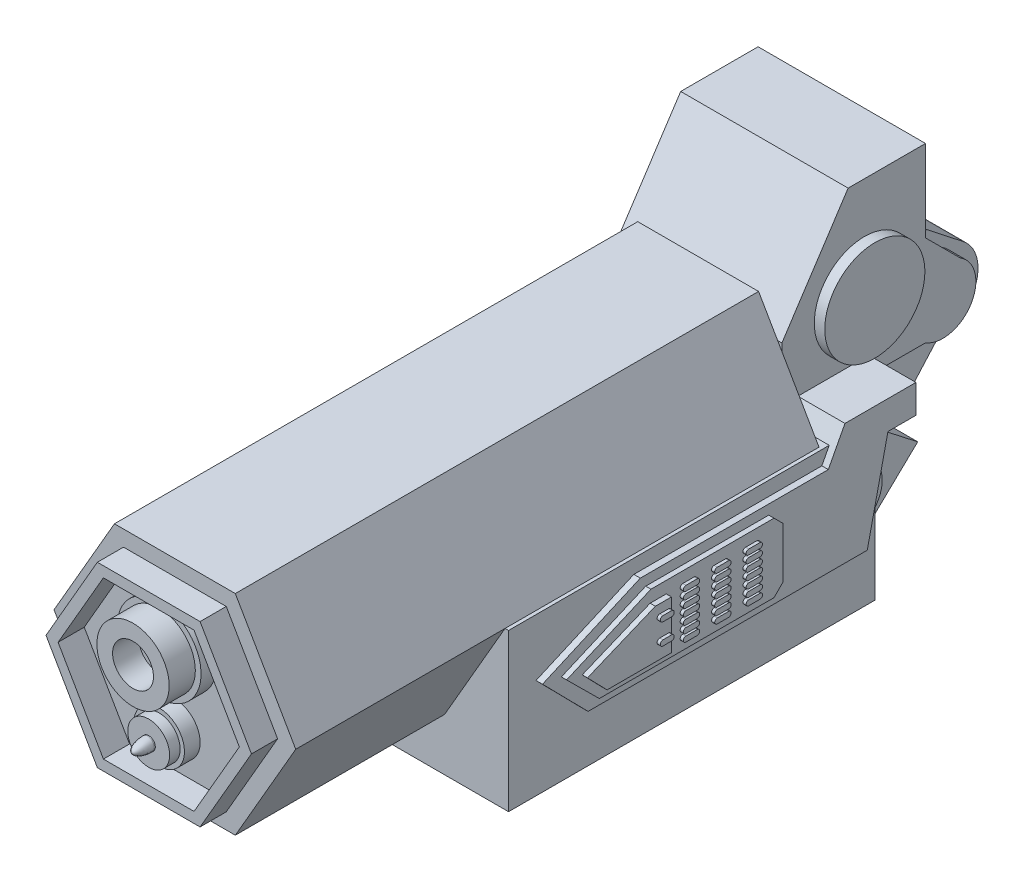
SolidWorks part; units mm, degrees
ref_plane "Front Plane" through (0, 0, 0) normal (0, 0, 1) x (1, 0, 0)
ref_plane "Top Plane" through (0, 0, 0) normal (0, 1, 0) x (1, 0, 0)
ref_plane "Right Plane" through (0, 0, 0) normal (1, 0, 0) x (0, 0, -1)
sketch "Sketch1" plane through (0, 0, 0) normal (0, 0, 1) x (1, 0, 0)
  line L0 (0, 0) -> (-46.0761, 0) construction
  line L1 (14.6647, 25.4) -> (-14.6647, 25.4)
  line L2 (-14.6647, 25.4) -> (-29.3294, 0)
  line L3 (-29.3294, 0) -> (-14.6647, -25.4)
  line L4 (-14.6647, -25.4) -> (14.6647, -25.4)
  line L5 (14.6647, -25.4) -> (29.3294, 0)
  line L6 (29.3294, 0) -> (14.6647, 25.4)
  circle A0 centre (0, 0) radius 25.4 construction
extrude "Boss-Extrude1" add sketch "Sketch1" against normal blind 127
sketch "Sketch2" plane through (0, 0, 0) normal (0, 0, 1) x (1, 0, 0)
  line L0 (14.6647, 25.4) -> (-14.6647, 25.4) construction
  line L1 (10.9985, 19.05) -> (-10.9985, 19.05)
  line L2 (-10.9985, 19.05) -> (-21.997, 0)
  line L3 (-21.997, 0) -> (-10.9985, -19.05)
  line L4 (-10.9985, -19.05) -> (10.9985, -19.05)
  line L5 (10.9985, -19.05) -> (21.997, 0)
  line L6 (21.997, 0) -> (10.9985, 19.05)
  circle A0 centre (0, 0) radius 19.05 construction
  dimension "D1" = 38.1
extrude "Extrude-Thin1" add sketch "Sketch2" along normal blind 6.35 thin thin type one direction wall 2.54
sketch "Sketch3" plane through (0, 0, 0) normal (0, 0, 1) x (1, 0, 0)
  line L0 (0, 0) -> (0, 26.4435) construction
  circle A0 centre (0, 8.1531) radius 10.16
  circle A1 centre (0, -10.2056) radius 6.131
extrude "Boss-Extrude2" add sketch "Sketch3" along normal blind 3.81
sketch "Sketch4" plane through (0, 0, 3.81) normal (0, 0, 1) x (1, 0, 0)
  circle A0 centre (0, 8.1531) radius 8.771
extrude "Extrude-Thin2" add sketch "Sketch4" along normal blind 6.35 thin thin type one direction reverse wall 3.81
sketch "Sketch5" plane through (0, 0, 3.81) normal (0, 0, 1) x (1, 0, 0)
  circle A0 centre (0, -10.2056) radius 5.08
extrude "Boss-Extrude3" add sketch "Sketch5" along normal blind 2.54
sketch "Sketch6" plane through (0, 0, 6.35) normal (0, 0, 1) x (1, 0, 0)
  circle A0 centre (0, -10.2056) radius 1.5996
extrude "Boss-Extrude4" add sketch "Sketch6" along normal blind 0.254
dome "Dome2" faces to dome 1 distance 3.81 reverse direction no elliptical dome yes face at (1.5996, -10.2056, 6.604) parameters "D1"=3.81
sketch "Sketch7" plane through (0, 0, 0) normal (0, 0, 1) x (1, 0, 0)
  line L0 (0, 0) -> (-37.4831, 0) construction
  line L1 (-30.3495, 0) -> (30.1809, 0)
  line L2 (-30.3495, 0) -> (-30.3495, -38.1)
  line L3 (-30.3495, -38.1) -> (30.1809, -38.1)
  line L4 (30.1809, 0) -> (30.1809, -38.1)
  dimension "D1" = 38.1
extrude "Boss-Extrude5" add sketch "Sketch7" against normal blind 88.9 from offset 50.8 offset against normal yes
sketch "Sketch8" plane through (0, 0, 0) normal (1, 0, 0) x (0, 0, -1)
  line L0 (139.7, -19.05) -> (156.755, -19.05)
  line L1 (139.7, 0) -> (139.7, -38.1) construction
  line L2 (156.755, -19.05) -> (169.6659, -4.4991)
  line L3 (139.7, -19.05) -> (139.7, 0)
  line L4 (139.7, 0) -> (166.5054, 19.2853)
  line L5 (166.5054, 19.2853) -> (175.4567, 12.2619)
  arc A0 (169.6659, -4.4991) -> (175.4567, 12.2619) centre (169.6661, 4.8817) ccw
extrude "Boss-Extrude6" add sketch "Sketch8" along normal blind 15.875 and the other way blind 15.875
sketch "Sketch9" plane through (0, 0, 0) normal (1, 0, 0) x (0, 0, -1)
  line L0 (127, 17.3963) -> (143.0783, 41.9028)
  line L1 (127, 25.4) -> (127, 0) construction
  line L2 (143.0783, 41.9028) -> (161.8606, 41.9028)
  line L3 (161.8606, 41.9028) -> (161.8606, 22.0472)
  line L4 (161.8606, 22.0472) -> (170.2679, 13.6399)
  line L5 (127, 17.3963) -> (127, 0)
  line L6 (127, 0) -> (161.8606, 0)
  arc A0 (161.8606, 0) -> (170.2679, 13.6399) centre (166.0643, 6.8199) ccw
extrude "Boss-Extrude7" add sketch "Sketch9" along normal blind 20.32 and the other way blind 20.32
sketch "Sketch10" plane through (0, 0, 0) normal (1, 0, 0) x (0, 0, -1)
  circle A0 centre (147.0136, 17.5982) radius 12.1559
extrude "Boss-Extrude8" add sketch "Sketch10" along normal blind 22.86 and the other way blind 22.86
sketch "Sketch11" plane through (0, 0, 0) normal (1, 0, 0) x (0, 0, -1)
  line L0 (139.7, -19.05) -> (139.7, -38.1)
  line L1 (139.7, -38.1) -> (156.4942, -38.1)
  line L2 (156.4942, -38.1) -> (167.5847, -27.4794)
  line L3 (167.5847, -27.4794) -> (156.755, -19.05)
  line L4 (156.755, -19.05) -> (139.7, -19.05)
extrude "Boss-Extrude9" add sketch "Sketch11" along normal blind 12.7 and the other way blind 12.7
sketch "Sketch12" plane through (0, 0, 0) normal (1, 0, 0) x (0, 0, -1)
  circle A0 centre (148.7813, -28.6662) radius 7.6511
extrude "Boss-Extrude10" add sketch "Sketch12" along normal blind 15.24 and the other way blind 15.24
sketch "Sketch13" plane through (0, -38.1, 0) normal (0, -1, 0) x (1, 0, 0)
  line L0 (0, -50.8) -> (0, -161.0568) construction
  line L1 (14.6647, -50.8) -> (-14.6647, -50.8) construction
  line L2 (-30.3495, -95.25) -> (33.7635, -95.25) construction
  line L3 (-30.3495, -139.7) -> (-30.3495, -50.8) construction
  line L5 (-17.9147, -147.0136) -> (17.9147, -147.0136)
  line L6 (-17.9147, -147.0136) -> (-17.9147, -64.8432)
  line L7 (-17.9147, -64.8432) -> (17.9147, -64.8432)
  line L8 (17.9147, -147.0136) -> (17.9147, -64.8432)
  line L9 (-17.9147, -147.0136) -> (17.9147, -64.8432) construction
  line L10 (-17.9147, -64.8432) -> (17.9147, -147.0136) construction
  point P9 (0, -105.9284)
ref_plane "Plane1" through (0, -57.15, 0) normal (0, -1, 0) x (1, 0, 0)
sketch "Sketch14" plane through (0, -57.15, 0) normal (0, -1, 0) x (1, 0, 0)
  line L1 (-8.56, -137.842) -> (8.56, -137.842)
  line L2 (-8.56, -137.842) -> (-8.56, -74.0148)
  line L3 (-8.56, -74.0148) -> (8.56, -74.0148)
  line L4 (8.56, -137.842) -> (8.56, -74.0148)
  line L5 (-8.56, -137.842) -> (8.56, -74.0148) construction
  line L6 (-8.56, -74.0148) -> (8.56, -137.842) construction
  point P0 (0, -105.9284)
loft "Loft1" add profiles "Sketch13", "Sketch14" connector at (17.9147, -38.1, -64.8432) connector at (8.56, -57.15, -74.0148)
sketch "Sketch15" plane through (0, 18.1746, -37.7498) normal (0, -0.4338, 0.901) x (1, 0, 0)
  line L0 (-10.7029, -62.4571) -> (0, -82.542)
  line L1 (-17.9147, -62.4571) -> (17.9147, -62.4571) construction
  line L2 (-10.7029, -62.4571) -> (10.7029, -62.4571)
  line L3 (17.9147, -62.4571) -> (-17.9147, -62.4571) construction
  line L4 (0, -62.4571) -> (0, -82.542) construction
  line L5 (10.7029, -62.4571) -> (0, -82.542)
extrude "Boss-Extrude11" add sketch "Sketch15" along normal blind 1.27
sketch "Sketch16" plane through (0, 17.6237, -36.6055) normal (0, -0.4338, 0.901) x (1, 0, 0)
  line L0 (10.7029, -62.4571) -> (-10.7029, -62.4571) construction
  line L1 (-10.7029, -62.4571) -> (-5.8753, -62.4571) construction
  line L2 (5.8753, -62.4571) -> (10.7029, -62.4571) construction
  line L3 (-5.8753, -62.4571) -> (5.8753, -62.4571)
  line L7 (-5.8753, -62.4571) -> (0, -79.4472)
  line L8 (0, -79.4472) -> (5.8753, -62.4571)
extrude "Boss-Extrude12" add sketch "Sketch16" along normal blind 2.54
fillet "Fillet1" radius 1.27 2 edges at (0, -56.4722, -72.9837) (0, -54.5102, -69.9248)
sketch "Sketch17" plane through (0, 0, 0) normal (1, 0, 0) x (0, 0, -1)
  line L0 (68.5306, -25.0933) -> (136.2912, -25.0933)
  line L1 (136.2912, -25.0933) -> (141.3068, -2.6485)
  line L2 (148.0979, -2.6485) -> (148.0979, 4.2639)
  line L3 (148.0979, 4.2639) -> (130.8775, 4.2639)
  line L4 (130.8775, 4.2639) -> (126.8356, -3.4158)
  line L5 (126.8356, -3.4158) -> (81.2052, -3.4158)
  line L6 (81.2052, -3.4158) -> (57.4673, -13.8461)
  line L7 (57.4673, -13.8461) -> (68.5306, -25.0933)
  line L8 (148.0979, -2.6485) -> (141.3068, -2.6485)
extrude "Boss-Extrude13" add sketch "Sketch17" along normal blind 31.75 and the other way blind 31.75
sketch "Sketch18" plane through (-31.75, 0, 0) normal (-1, 0, 0) x (0, 0, 1)
  line L0 (-112.3819, -22.4812) -> (-69.988, -22.4812)
  line L1 (-69.988, -22.4812) -> (-62.0481, -14.5993)
  line L2 (-62.0481, -14.5993) -> (-82.5216, -5.7665)
  line L3 (-82.5216, -5.7665) -> (-112.3819, -5.7665)
  line L4 (-114.5712, -7.9558) -> (-114.5712, -20.2918)
  line L5 (-112.3819, -5.7665) -> (-114.5712, -7.9558)
  line L6 (-114.5712, -20.2918) -> (-112.3819, -22.4812)
extrude "Boss-Extrude14" add sketch "Sketch18" along normal blind 1.27
sketch "Sketch19" plane through (-33.02, 0, 0) normal (-1, 0, 0) x (0, 0, 1)
  line L0 (-86.2319, -20.3383) -> (-70.6018, -20.3383)
  line L1 (-70.6018, -20.3383) -> (-65.8448, -15.4356)
  line L2 (-65.8448, -15.4356) -> (-82.3244, -8.6157)
  line L3 (-82.3244, -8.6157) -> (-86.2319, -8.6157)
  line L4 (-86.2319, -8.6157) -> (-86.2319, -20.3383)
extrude "Boss-Extrude15" add sketch "Sketch19" along normal blind 1.27
sketch "Sketch20" plane through (-34.29, 0, 0) normal (-1, 0, 0) x (0, 0, 1)
  line L0 (-85.4907, -11.4026) -> (-83.3959, -11.4026) construction
  line L1 (-85.4907, -10.752) -> (-83.3959, -10.752)
  line L2 (-85.4907, -12.0533) -> (-83.3959, -12.0533)
  line L3 (-85.4907, -16.4826) -> (-83.3959, -16.4826) construction
  line L4 (-85.4907, -15.832) -> (-83.3959, -15.832)
  line L5 (-85.4907, -17.1333) -> (-83.3959, -17.1333)
  arc A0 (-85.4907, -10.752) -> (-85.4907, -12.0533) centre (-85.4907, -11.4026) ccw
  arc A1 (-83.3959, -12.0533) -> (-83.3959, -10.752) centre (-83.3959, -11.4026) ccw
  arc A2 (-85.4907, -15.832) -> (-85.4907, -17.1333) centre (-85.4907, -16.4826) ccw
  arc A3 (-83.3959, -17.1333) -> (-83.3959, -15.832) centre (-83.3959, -16.4826) ccw
  point P2 (-84.4433, -11.4026)
  point P9 (-84.4433, -16.4826)
extrude "Boss-Extrude16" add sketch "Sketch20" along normal blind 0.762
sketch "Sketch21" plane through (-33.02, 0, 0) normal (-1, 0, 0) x (0, 0, 1)
  line L0 (-108.2132, -9.0607) -> (-105.483, -9.0607) construction
  line L1 (-108.2132, -8.4322) -> (-105.483, -8.4322)
  line L2 (-108.2132, -9.6892) -> (-105.483, -9.6892)
  line L3 (-100.5932, -9.0607) -> (-97.863, -9.0607) construction
  line L4 (-100.5932, -8.4322) -> (-97.863, -8.4322)
  line L5 (-100.5932, -9.6892) -> (-97.863, -9.6892)
  line L6 (-92.9732, -9.0607) -> (-90.243, -9.0607) construction
  line L7 (-92.9732, -8.4322) -> (-90.243, -8.4322)
  line L8 (-92.9732, -9.6892) -> (-90.243, -9.6892)
  line L9 (-108.2132, -10.8387) -> (-105.483, -10.8387) construction
  line L10 (-108.2132, -10.2102) -> (-105.483, -10.2102)
  line L11 (-108.2132, -11.4672) -> (-105.483, -11.4672)
  line L12 (-100.5932, -10.8387) -> (-97.863, -10.8387) construction
  line L13 (-100.5932, -10.2102) -> (-97.863, -10.2102)
  line L14 (-100.5932, -11.4672) -> (-97.863, -11.4672)
  line L15 (-92.9732, -10.8387) -> (-90.243, -10.8387) construction
  line L16 (-92.9732, -10.2102) -> (-90.243, -10.2102)
  line L17 (-92.9732, -11.4672) -> (-90.243, -11.4672)
  line L18 (-108.2132, -12.6167) -> (-105.483, -12.6167) construction
  line L19 (-108.2132, -11.9882) -> (-105.483, -11.9882)
  line L20 (-108.2132, -13.2452) -> (-105.483, -13.2452)
  line L21 (-100.5932, -12.6167) -> (-97.863, -12.6167) construction
  line L22 (-100.5932, -11.9882) -> (-97.863, -11.9882)
  line L23 (-100.5932, -13.2452) -> (-97.863, -13.2452)
  line L24 (-92.9732, -12.6167) -> (-90.243, -12.6167) construction
  line L25 (-92.9732, -11.9882) -> (-90.243, -11.9882)
  line L26 (-92.9732, -13.2452) -> (-90.243, -13.2452)
  line L27 (-108.2132, -14.3947) -> (-105.483, -14.3947) construction
  line L28 (-108.2132, -13.7662) -> (-105.483, -13.7662)
  line L29 (-108.2132, -15.0232) -> (-105.483, -15.0232)
  line L30 (-100.5932, -14.3947) -> (-97.863, -14.3947) construction
  line L31 (-100.5932, -13.7662) -> (-97.863, -13.7662)
  line L32 (-100.5932, -15.0232) -> (-97.863, -15.0232)
  line L33 (-92.9732, -14.3947) -> (-90.243, -14.3947) construction
  line L34 (-92.9732, -13.7662) -> (-90.243, -13.7662)
  line L35 (-92.9732, -15.0232) -> (-90.243, -15.0232)
  line L36 (-108.2132, -16.1727) -> (-105.483, -16.1727) construction
  line L37 (-108.2132, -15.5442) -> (-105.483, -15.5442)
  line L38 (-108.2132, -16.8012) -> (-105.483, -16.8012)
  line L39 (-100.5932, -16.1727) -> (-97.863, -16.1727) construction
  line L40 (-100.5932, -15.5442) -> (-97.863, -15.5442)
  line L41 (-100.5932, -16.8012) -> (-97.863, -16.8012)
  line L42 (-92.9732, -16.1727) -> (-90.243, -16.1727) construction
  line L43 (-92.9732, -15.5442) -> (-90.243, -15.5442)
  line L44 (-92.9732, -16.8012) -> (-90.243, -16.8012)
  line L45 (-108.2132, -17.9507) -> (-105.483, -17.9507) construction
  line L46 (-108.2132, -17.3222) -> (-105.483, -17.3222)
  line L47 (-108.2132, -18.5792) -> (-105.483, -18.5792)
  line L48 (-100.5932, -17.9507) -> (-97.863, -17.9507) construction
  line L49 (-100.5932, -17.3222) -> (-97.863, -17.3222)
  line L50 (-100.5932, -18.5792) -> (-97.863, -18.5792)
  line L51 (-92.9732, -17.9507) -> (-90.243, -17.9507) construction
  line L52 (-92.9732, -17.3222) -> (-90.243, -17.3222)
  line L53 (-92.9732, -18.5792) -> (-90.243, -18.5792)
  line L54 (-108.2132, -19.7287) -> (-105.483, -19.7287) construction
  line L55 (-108.2132, -19.1002) -> (-105.483, -19.1002)
  line L56 (-108.2132, -20.3572) -> (-105.483, -20.3572)
  line L57 (-100.5932, -19.7287) -> (-97.863, -19.7287) construction
  line L58 (-100.5932, -19.1002) -> (-97.863, -19.1002)
  line L59 (-100.5932, -20.3572) -> (-97.863, -20.3572)
  line L60 (-92.9732, -19.7287) -> (-90.243, -19.7287) construction
  line L61 (-92.9732, -19.1002) -> (-90.243, -19.1002)
  line L62 (-92.9732, -20.3572) -> (-90.243, -20.3572)
  arc A0 (-108.2132, -8.4322) -> (-108.2132, -9.6892) centre (-108.2132, -9.0607) ccw
  arc A1 (-105.483, -9.6892) -> (-105.483, -8.4322) centre (-105.483, -9.0607) ccw
  arc A2 (-100.5932, -8.4322) -> (-100.5932, -9.6892) centre (-100.5932, -9.0607) ccw
  arc A3 (-97.863, -9.6892) -> (-97.863, -8.4322) centre (-97.863, -9.0607) ccw
  arc A4 (-92.9732, -8.4322) -> (-92.9732, -9.6892) centre (-92.9732, -9.0607) ccw
  arc A5 (-90.243, -9.6892) -> (-90.243, -8.4322) centre (-90.243, -9.0607) ccw
  arc A6 (-108.2132, -10.2102) -> (-108.2132, -11.4672) centre (-108.2132, -10.8387) ccw
  arc A7 (-105.483, -11.4672) -> (-105.483, -10.2102) centre (-105.483, -10.8387) ccw
  arc A8 (-100.5932, -10.2102) -> (-100.5932, -11.4672) centre (-100.5932, -10.8387) ccw
  arc A9 (-97.863, -11.4672) -> (-97.863, -10.2102) centre (-97.863, -10.8387) ccw
  arc A10 (-92.9732, -10.2102) -> (-92.9732, -11.4672) centre (-92.9732, -10.8387) ccw
  arc A11 (-90.243, -11.4672) -> (-90.243, -10.2102) centre (-90.243, -10.8387) ccw
  arc A12 (-108.2132, -11.9882) -> (-108.2132, -13.2452) centre (-108.2132, -12.6167) ccw
  arc A13 (-105.483, -13.2452) -> (-105.483, -11.9882) centre (-105.483, -12.6167) ccw
  arc A14 (-100.5932, -11.9882) -> (-100.5932, -13.2452) centre (-100.5932, -12.6167) ccw
  arc A15 (-97.863, -13.2452) -> (-97.863, -11.9882) centre (-97.863, -12.6167) ccw
  arc A16 (-92.9732, -11.9882) -> (-92.9732, -13.2452) centre (-92.9732, -12.6167) ccw
  arc A17 (-90.243, -13.2452) -> (-90.243, -11.9882) centre (-90.243, -12.6167) ccw
  arc A18 (-108.2132, -13.7662) -> (-108.2132, -15.0232) centre (-108.2132, -14.3947) ccw
  arc A19 (-105.483, -15.0232) -> (-105.483, -13.7662) centre (-105.483, -14.3947) ccw
  arc A20 (-100.5932, -13.7662) -> (-100.5932, -15.0232) centre (-100.5932, -14.3947) ccw
  arc A21 (-97.863, -15.0232) -> (-97.863, -13.7662) centre (-97.863, -14.3947) ccw
  arc A22 (-92.9732, -13.7662) -> (-92.9732, -15.0232) centre (-92.9732, -14.3947) ccw
  arc A23 (-90.243, -15.0232) -> (-90.243, -13.7662) centre (-90.243, -14.3947) ccw
  arc A24 (-108.2132, -15.5442) -> (-108.2132, -16.8012) centre (-108.2132, -16.1727) ccw
  arc A25 (-105.483, -16.8012) -> (-105.483, -15.5442) centre (-105.483, -16.1727) ccw
  arc A26 (-100.5932, -15.5442) -> (-100.5932, -16.8012) centre (-100.5932, -16.1727) ccw
  arc A27 (-97.863, -16.8012) -> (-97.863, -15.5442) centre (-97.863, -16.1727) ccw
  arc A28 (-92.9732, -15.5442) -> (-92.9732, -16.8012) centre (-92.9732, -16.1727) ccw
  arc A29 (-90.243, -16.8012) -> (-90.243, -15.5442) centre (-90.243, -16.1727) ccw
  arc A30 (-108.2132, -17.3222) -> (-108.2132, -18.5792) centre (-108.2132, -17.9507) ccw
  arc A31 (-105.483, -18.5792) -> (-105.483, -17.3222) centre (-105.483, -17.9507) ccw
  arc A32 (-100.5932, -17.3222) -> (-100.5932, -18.5792) centre (-100.5932, -17.9507) ccw
  arc A33 (-97.863, -18.5792) -> (-97.863, -17.3222) centre (-97.863, -17.9507) ccw
  arc A34 (-92.9732, -17.3222) -> (-92.9732, -18.5792) centre (-92.9732, -17.9507) ccw
  arc A35 (-90.243, -18.5792) -> (-90.243, -17.3222) centre (-90.243, -17.9507) ccw
  arc A36 (-108.2132, -19.1002) -> (-108.2132, -20.3572) centre (-108.2132, -19.7287) ccw
  arc A37 (-105.483, -20.3572) -> (-105.483, -19.1002) centre (-105.483, -19.7287) ccw
  arc A38 (-100.5932, -19.1002) -> (-100.5932, -20.3572) centre (-100.5932, -19.7287) ccw
  arc A39 (-97.863, -20.3572) -> (-97.863, -19.1002) centre (-97.863, -19.7287) ccw
  arc A40 (-92.9732, -19.1002) -> (-92.9732, -20.3572) centre (-92.9732, -19.7287) ccw
  arc A41 (-90.243, -20.3572) -> (-90.243, -19.1002) centre (-90.243, -19.7287) ccw
  point P2 (-106.8481, -9.0607)
  point P12 (-99.2281, -9.0607)
  point P19 (-91.6081, -9.0607)
  point P26 (-106.8481, -10.8387)
  point P33 (-99.2281, -10.8387)
  point P40 (-91.6081, -10.8387)
  point P47 (-106.8481, -12.6167)
  point P54 (-99.2281, -12.6167)
  point P61 (-91.6081, -12.6167)
  point P68 (-106.8481, -14.3947)
  point P75 (-99.2281, -14.3947)
  point P82 (-91.6081, -14.3947)
  point P89 (-106.8481, -16.1727)
  point P96 (-99.2281, -16.1727)
  point P103 (-91.6081, -16.1727)
  point P110 (-106.8481, -17.9507)
  point P117 (-99.2281, -17.9507)
  point P124 (-91.6081, -17.9507)
  point P131 (-106.8481, -19.7287)
  point P138 (-99.2281, -19.7287)
  point P145 (-91.6081, -19.7287)
  dimension "D1" = 3
  dimension "D2" = 7
extrude "Boss-Extrude17" add sketch "Sketch21" along normal blind 0.762
mirror "Mirror1" about plane through (0, 0, 0) normal (1, 0, 0) of "Boss-Extrude17", "Boss-Extrude16", "Boss-Extrude15", "Boss-Extrude14"
sketch "Sketch23" plane through (0, 41.9028, 0) normal (0, 1, 0) x (1, 0, 0)
  circle A0 centre (0.4299, 152.4) radius 6.531 construction
